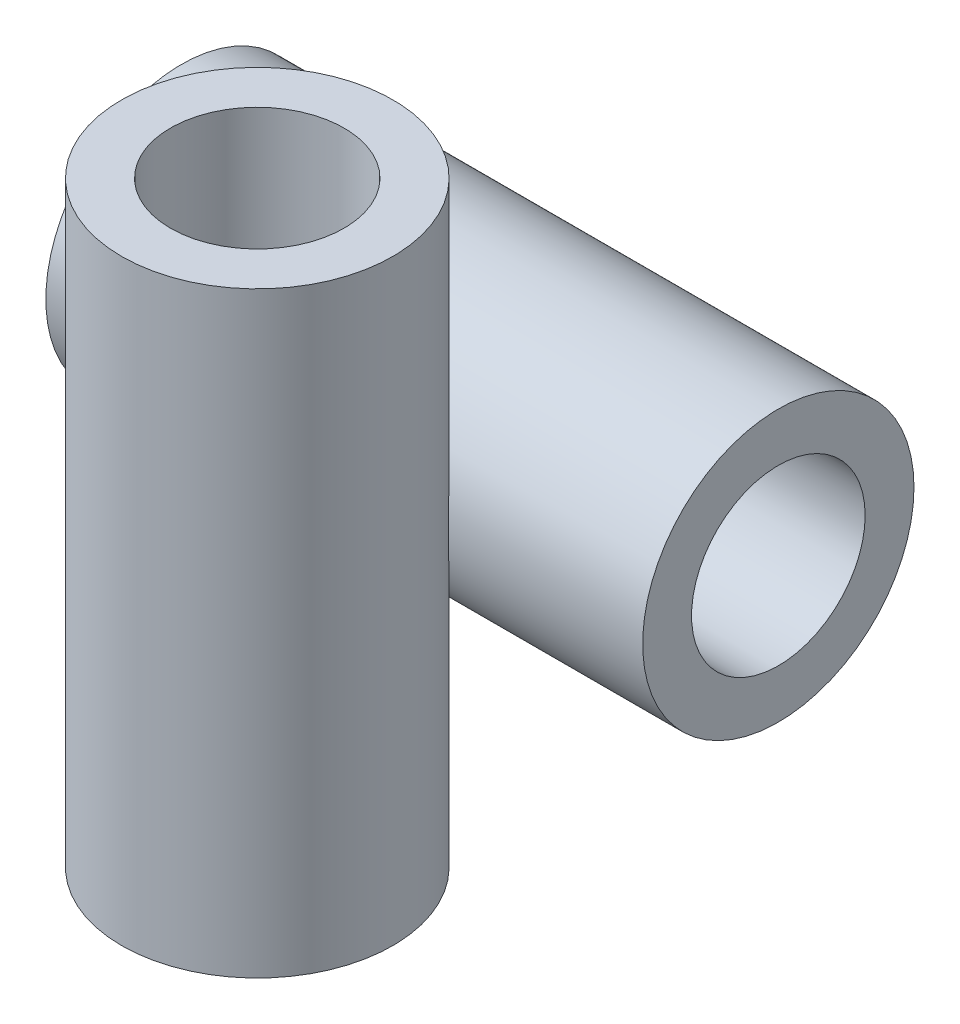
SolidWorks part; units mm, degrees
ref_plane "Front Plane" through (0, 0, 0) normal (0, 0, 1) x (1, 0, 0)
ref_plane "Top Plane" through (0, 0, 0) normal (0, 1, 0) x (1, 0, 0)
ref_plane "Right Plane" through (0, 0, 0) normal (1, 0, 0) x (0, 0, -1)
sketch "Sketch2" plane through (0, 0, 0) normal (0, 1, 0) x (1, 0, 0)
  circle A0 centre (0, 0) radius 25
  circle A1 centre (0, 0) radius 16
extrude "Boss-Extrude1" add sketch "Sketch2" along normal blind 110
sketch "Sketch3" plane through (0, 0, 0) normal (1, 0, 0) x (0, 0, -1)
  line L0 (-25, 55) -> (25, 55)
  line L1 (-25, 110) -> (-25, 0) construction
  line L2 (25, 0) -> (25, 110) construction
  circle A0 centre (41.0317, 55.1453) radius 25
  circle A2 centre (41.0317, 55.1453) radius 16
extrude "Boss-Extrude3" add sketch "Sketch3" along normal blind 55 and the other way blind 55 contours A0
sketch "Sketch5" plane through (55, 0, 0) normal (1, 0, 0) x (0, 0, -1)
  circle A0 centre (41.0317, 55.1453) radius 16
extrude "Cut-Extrude2" cut sketch "Sketch5" against normal blind 110
